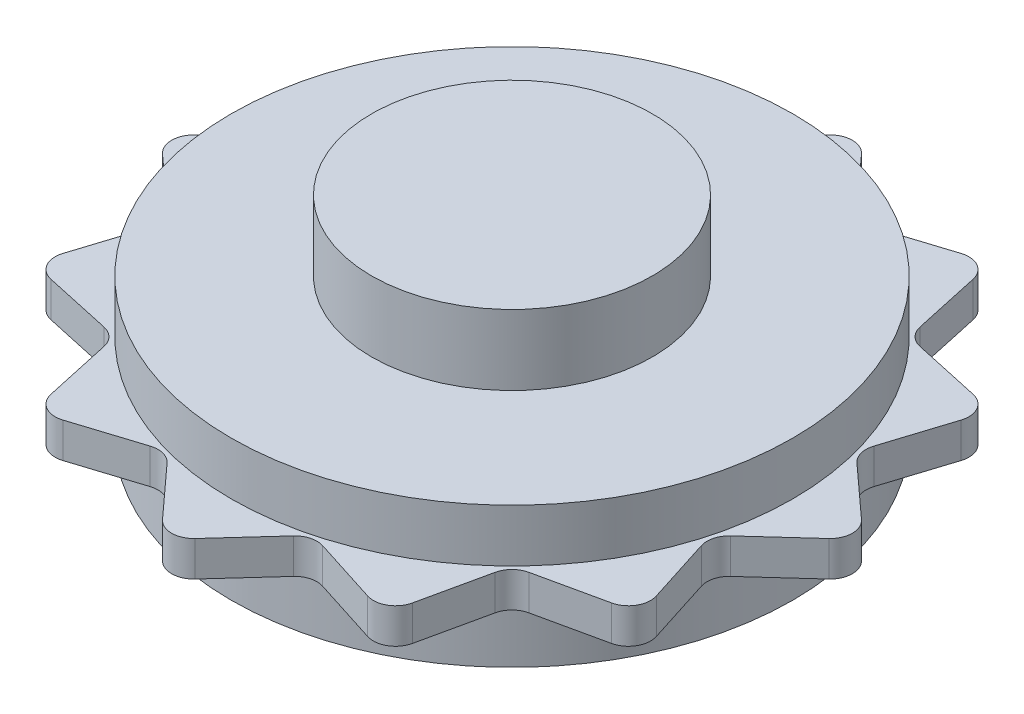
SolidWorks part; units mm, degrees
ref_plane "Front Plane" through (0, 0, 0) normal (0, 0, 1) x (1, 0, 0)
ref_plane "Top Plane" through (0, 0, 0) normal (0, 1, 0) x (1, 0, 0)
ref_plane "Right Plane" through (0, 0, 0) normal (1, 0, 0) x (0, 0, -1)
sketch "Sketch1" plane through (0, 0, 0) normal (0, 1, 0) x (1, 0, 0)
  circle A0 centre (0, 0) radius 6.35
  dimension "D1" = 12.7
extrude "Boss-Extrude1" add sketch "Sketch1" along normal mid plane 12.7 from surface starting at plane "Top Plane"
sketch "Sketch2" plane through (0, 0, 0) normal (0, 1, 0) x (1, 0, 0)
  circle A0 centre (0, 0) radius 12.7
  dimension "D1" = 25.4
extrude "Boss-Extrude2" add sketch "Sketch2" along normal mid plane 6.35 from surface starting at plane "Top Plane"
ref_plane "Plane1" through (0, 0, 0) normal (0, 1, 0) x (1, 0, 0)
sketch "Sketch3" plane through (0, 0, 0) normal (0, 1, 0) x (1, 0, 0)
  line L0 (0, 0) -> (0, -15.875) construction
  line L1 (0, 0) -> (-4.4774, -16.7099) construction
  line L2 (-3.287, -12.2673) -> (0, -15.875) construction
  line L3 (0, 0) -> (-9.078, -15.7235) construction
  line L4 (-3.287, -12.2673) -> (-7.9375, -13.7482) construction
  line L5 (-6.8917, -13.4151) -> (-3.8979, -12.4618)
  line L6 (-2.8552, -12.7412) -> (-0.7392, -15.0637)
  line L7 (-7.6951, -13.3283) -> (-6.35, -10.9985)
  line L8 (-6.35, -10.9985) -> (0, -12.7)
  line L9 (0, -12.7) -> (0, -15.3902)
  circle A0 centre (0, 0) radius 12.7 construction
  arc A1 (-0.7392, -15.0637) -> (0, -15.3902) centre (0, -14.3902) ccw
  circle A2 centre (0, 0) radius 15.875 construction
  arc A3 (-7.6951, -13.3283) -> (-6.8917, -13.4151) centre (-7.1951, -12.4623) ccw
  arc A4 (-3.8979, -12.4618) -> (-2.8552, -12.7412) centre (-3.5944, -13.4146) cw
  point P14 (-0.7392, -15.0637)
  dimension "D3" = 1
  dimension "D2" = 3.175
  dimension "D5" = 1
  dimension "D6" = 1
  dimension "D1" = 15
  dimension "D4" = 15
extrude "Boss-Extrude3" add sketch "Sketch3" along normal mid plane 1.5875
pattern_circular "CirPattern1" count 12 over 360 about axis through (0, 3.175, 0) along (0, -1, 0) of "Boss-Extrude3"
